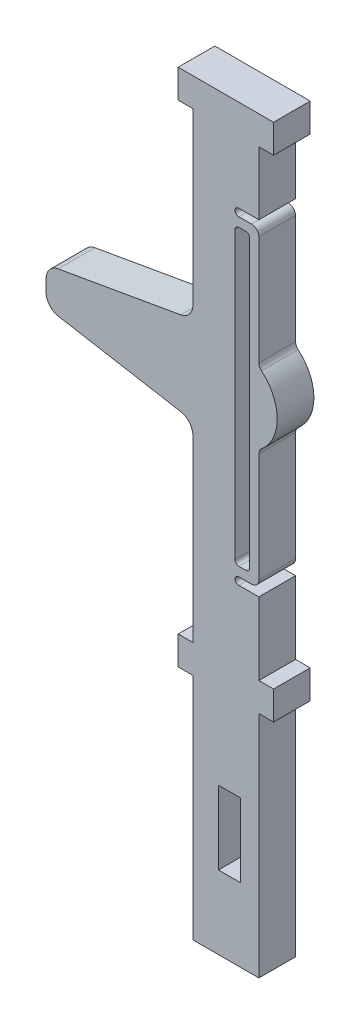
SolidWorks part; units mm, degrees
ref_plane "Front Plane" through (0, 0, 0) normal (0, 0, 1) x (1, 0, 0)
ref_plane "Top Plane" through (0, 0, 0) normal (0, 1, 0) x (1, 0, 0)
ref_plane "Right Plane" through (0, 0, 0) normal (1, 0, 0) x (0, 0, -1)
sketch "Sketch1" plane through (0, 0, 0) normal (0, 0, 1) x (1, 0, 0)
  line L0 (-18.6, 130.08) -> (-18.6, 133.58)
  line L1 (-18.6, 198.9746) -> (-18.6, 200.4746)
  line L2 (-18.6, 166.58) -> (-18.6, 182.9566)
  line L3 (-18.6, 94.4746) -> (-18.6, 125.6853)
  line L4 (-18.6, 200.4746) -> (-16.6, 200.4746) construction
  line L5 (-18.6, 70.4746) -> (-18.6, 71.9746)
  line L6 (-27.6, 94.4746) -> (-18.6, 94.4746)
  line L7 (-22.1, 161.7066) -> (-16.1, 161.7066) construction
  line L8 (-19.85, 181.7066) -> (-21.85, 181.7066)
  line L9 (-19.85, 181.7066) -> (-19.85, 141.7066)
  line L10 (-19.85, 141.7066) -> (-21.85, 141.7066)
  line L11 (-21.85, 181.7066) -> (-21.85, 141.7066)
  line L12 (-19.85, 181.7066) -> (-21.85, 141.7066) construction
  line L13 (-19.85, 141.7066) -> (-21.85, 181.7066) construction
  line L14 (-18.6, 182.9566) -> (-21.85, 182.9566)
  line L15 (-21.85, 182.9566) -> (-21.85, 183.9566)
  line L16 (-21.85, 183.9566) -> (-18.6, 183.9566)
  line L17 (-18.6, 183.9566) -> (-18.6, 192.58)
  line L18 (-19.85, 181.7066) -> (-18.6, 181.7066) construction
  line L19 (-19.85, 181.7066) -> (-19.85, 182.9566) construction
  line L20 (-18.6, 140.4566) -> (-21.85, 140.4566)
  line L21 (-21.85, 140.4566) -> (-21.85, 139.4566)
  line L22 (-21.85, 139.4566) -> (-18.6, 139.4566)
  line L23 (-19.85, 141.7066) -> (-18.6, 141.7066) construction
  line L24 (-19.85, 141.7066) -> (-19.85, 140.4566) construction
  line L25 (-18.6, 140.4566) -> (-18.6, 156.8332)
  line L26 (-15, 136) -> (-15, 164) construction
  line L27 (-15, 136) -> (-15, 164) construction
  line L28 (-15, 150) -> (-18.6, 150) construction
  line L30 (-16.6, 196.4746) -> (-16.6, 192.58)
  line L31 (-16.6, 192.58) -> (-18.6, 192.58)
  line L32 (-16.6, 168.58) -> (-18.6, 168.58) construction
  line L33 (-16.6, 168.58) -> (-18.6, 168.58) construction
  line L35 (-16.6, 196.4746) -> (-29.6, 196.4746)
  line L36 (-29.6, 196.4746) -> (-29.6, 192.58)
  line L37 (-29.6, 192.58) -> (-27.6, 192.58)
  line L38 (-27.6, 192.58) -> (-27.6, 167.7066)
  line L39 (-18.6, 129.58) -> (-16.6, 129.58)
  line L40 (-16.6, 129.58) -> (-16.6, 125.6853)
  line L41 (-16.6, 125.6853) -> (-18.6, 125.6853)
  line L42 (-16.6, 133.58) -> (-18.6, 133.58) construction
  line L43 (-16.6, 133.58) -> (-18.6, 133.58) construction
  line L44 (-18.6, 129.58) -> (-18.6, 139.4566)
  line L45 (-27.6, 129.58) -> (-29.6, 129.58)
  line L46 (-29.6, 129.58) -> (-29.6, 125.6853)
  line L47 (-29.6, 125.6853) -> (-27.6, 125.6853)
  line L48 (-27.6, 125.6853) -> (-27.6, 94.4746)
  line L49 (-27.6, 167.7066) -> (-47.6, 164.2066)
  line L50 (-47.6, 164.2066) -> (-47.6, 159.2066)
  line L51 (-47.6, 159.2066) -> (-27.6, 155.7066)
  line L52 (-47.6, 161.7066) -> (-27.6, 161.7066) construction
  line L53 (-27.6, 155.7066) -> (-27.6, 129.58)
  line L54 (-27.6, 167.7066) -> (-27.6, 155.7066) construction
  line L55 (-22.6, 114.4746) -> (-22.6, 104.4746) construction
  line L56 (-21.1, 114.4746) -> (-24.1, 114.4746)
  line L57 (-21.1, 114.4746) -> (-21.1, 104.4746)
  line L58 (-21.1, 104.4746) -> (-24.1, 104.4746)
  line L59 (-24.1, 114.4746) -> (-24.1, 104.4746)
  line L60 (-21.1, 114.4746) -> (-24.1, 104.4746) construction
  line L61 (-21.1, 104.4746) -> (-24.1, 114.4746) construction
  line L62 (-18.6, 80.4746) -> (-18.6, 105.1853)
  line L63 (-18.6, 70.4746) -> (-16.6, 70.4746) construction
  line L64 (-18.6, 198.9746) -> (-18.6, 172.08)
  arc A0 (-18.6, 156.8332) -> (-18.6, 166.58) centre (-22.1, 161.7066) ccw
  point P4 (-20.85, 161.7066)
  point P59 (-22.6, 109.4746)
  dimension "D1" = 6
  dimension "D2" = 3.5
  dimension "D3" = 2
  dimension "D4" = 1.25
  dimension "D5" = 2
  dimension "D6" = 40
  dimension "D7" = 4
  dimension "D8" = 24
  dimension "D9" = 1
  dimension "D10" = 24
  dimension "D11" = 9
  dimension "D12" = 4
  dimension "D13" = 5
  dimension "D14" = 12
  dimension "D15" = 20
  dimension "D16" = 3
  dimension "D17" = 10
  dimension "D18" = 10
  dimension "D19" = 2.5
extrude "Boss-Extrude1" add sketch "Sketch1" along normal mid plane 5
fillet "Fillet1" radius 0.5 8 edges at (-21.85, 183.9566, 0) (-19.85, 141.7066, 0) (-21.85, 139.4566, 0) (-21.85, 140.4566, 0) (-21.85, 141.7066, 0) (-21.85, 182.9566, 0) (-21.85, 181.7066, 0) (-19.85, 181.7066, 0)
fillet "Fillet2" radius 1 2 edges at (-18.6, 140.4566, 0) (-18.6, 182.9566, 0)
fillet "Fillet3" radius 1 2 edges at (-18.6, 156.8332, 0) (-18.6, 166.58, 0)
fillet "Fillet4" radius 2 4 edges at (-47.6, 159.2066, 0) (-47.6, 164.2066, 0) (-27.6, 167.7066, 0) (-27.6, 155.7066, 0)
